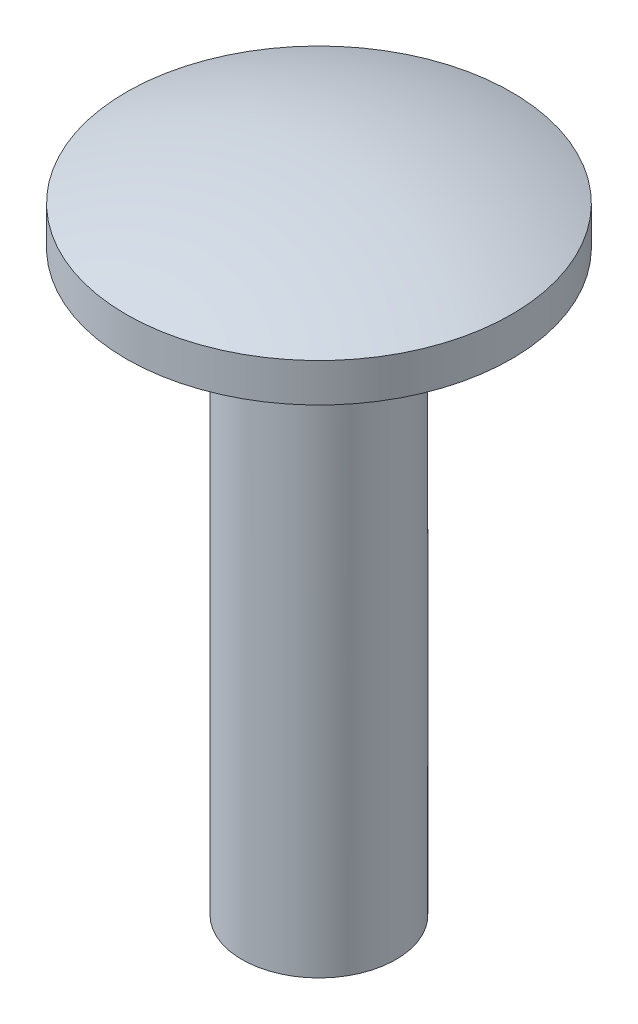
SolidWorks part; units mm, degrees
ref_plane "Piano frontale" through (0, 0, 0) normal (0, 0, 1) x (1, 0, 0)
ref_plane "Piano superiore" through (0, 0, 0) normal (0, 1, 0) x (1, 0, 0)
ref_plane "Piano destro" through (0, 0, 0) normal (1, 0, 0) x (0, 0, -1)
sketch "Schizzo1" plane through (0, 0, 0) normal (0, 1, 0) x (1, 0, 0)
  circle A0 centre (0, 0) radius 5
  dimension "D1" = 10
extrude "Estrusione1" add sketch "Schizzo1" along normal blind 1
dome "Cupola1" faces to dome 1 distance 1 reverse direction no elliptical dome no face at (0, 1, 5) parameters "D1"=1
sketch "Schizzo2" plane through (0, 0, 0) normal (0, -1, 0) x (1, 0, 0)
  circle A0 centre (0, 0) radius 2
  dimension "D1" = 4
extrude "Estrusione2" add sketch "Schizzo2" along normal blind 15
sketch "Schizzo3" plane through (0, 0, 0) normal (0, 0, 1) x (1, 0, 0)
  circle A0 centre (0, -0.75) radius 0.75
  dimension "D1" = 1.5
extrude "Taglio-Estrusione1" cut sketch "Schizzo3" against normal through all and the other way through all
ref_axis "Asse1" through (0, -0.75, 2) along (0, 0, -1)
